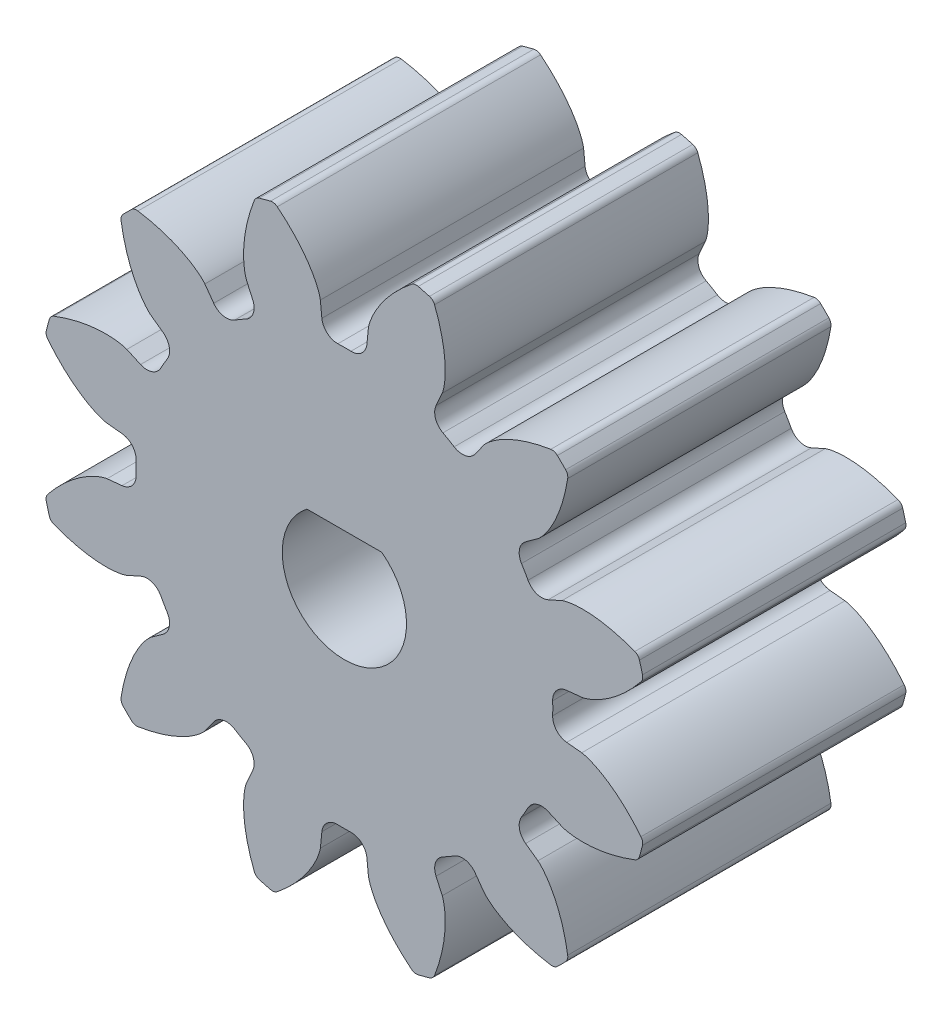
SolidWorks part; units mm, degrees
material "DELRIN"
ref_plane "Front" through (0, 0, 0) normal (0, 0, 1) x (1, 0, 0)
ref_plane "Top" through (0, 0, 0) normal (0, 1, 0) x (1, 0, 0)
ref_plane "Right" through (0, 0, 0) normal (1, 0, 0) x (0, 0, -1)
sketch "Sketch1" plane through (0, 0, 0) normal (0, 0, 1) x (1, 0, 0)
  circle A0 centre (0, 0) radius 14.8167
  dimension "OutsideDiameter" = 29.6333
extrude "Boss-Extrude1" add sketch "Sketch1" along normal blind 12.7
sketch "Sketch3" plane through (0, 0, 0) normal (0, 0, 1) x (1, 0, 0)
  line L0 (0, 0) -> (43.7181, 0) construction
  line L2 (0, 0) -> (-1.013, 10.003) construction
  line L3 (0, 0) -> (1.013, 10.003) construction
  line L4 (1.013, 10.003) -> (1.1597, 11.4515) construction
  line L5 (0, 0) -> (0, 61.276) construction
  line L6 (-1.013, 10.003) -> (-1.1597, 11.4515) construction
  circle A0 centre (0, 0) radius 14.8167 construction
  circle A1 centre (0, 0) radius 12.7 construction
  circle A2 centre (0, 0) radius 11.5101 construction
  arc A3 (1.013, 10.003) -> (-1.013, 10.003) centre (0, 0) ccw construction
  arc A5 (3.383, 14.4253) -> (-3.383, 14.4253) centre (0, 0) ccw
  spline S0 degree 4 poles (-1.1597, 11.4515) (-1.1603, 11.4571) (-1.1625, 11.4726) (-1.1677, 11.5019) (-1.1778, 11.5493) (-1.1932, 11.6092) (-1.2157, 11.6861) (-1.2458, 11.7758) (-1.2825, 11.8733) (-1.3264, 11.9783) (-1.3735, 12.0819) (-1.4237, 12.1841) (-1.4765, 12.2849) (-1.5438, 12.4057) (-1.629, 12.5486) (-1.7352, 12.7127) (-1.8633, 12.8952) (-2.0018, 13.0771) (-2.1447, 13.2526) (-2.2964, 13.4256) (-2.4483, 13.5899) (-2.6134, 13.7559) (-2.7695, 13.9068) (-2.9521, 14.0704) (-3.1018, 14.2009) (-3.3074, 14.367) (-3.4312, 14.4633) (-3.5787, 14.5738) (-3.6457, 14.6217) (-3.6869, 14.6513) knots 0 0 0 0 0 0.005377 0.015084 0.028532 0.04661 0.064855 0.092111 0.119476 0.146842 0.174209 0.201575 0.228941 0.256307 0.307035 0.361767 0.4165 0.471232 0.525964 0.580697 0.635429 0.690161 0.744894 0.799626 0.854358 0.909091 0.954545 1 1 1 1 1 construction
  spline S1 degree 4 poles (-1.1597, 11.4515) (-1.1603, 11.4571) (-1.1625, 11.4726) (-1.1677, 11.5019) (-1.1778, 11.5493) (-1.1932, 11.6092) (-1.2157, 11.6861) (-1.2458, 11.7758) (-1.2825, 11.8733) (-1.3264, 11.9783) (-1.3735, 12.0819) (-1.4237, 12.1841) (-1.4765, 12.2849) (-1.5438, 12.4057) (-1.629, 12.5486) (-1.7352, 12.7127) (-1.8633, 12.8952) (-2.0018, 13.0771) (-2.1447, 13.2526) (-2.2964, 13.4256) (-2.4483, 13.5899) (-2.6134, 13.7559) (-2.7695, 13.9068) (-2.9521, 14.0704) (-3.1018, 14.2009) (-3.2628, 14.331) (-3.3421, 14.3936) (-3.383, 14.4253) knots 0 0 0 0 0 0.005377 0.015084 0.028532 0.04661 0.064855 0.092111 0.119476 0.146842 0.174209 0.201575 0.228941 0.256307 0.307035 0.361767 0.4165 0.471232 0.525964 0.580697 0.635429 0.690161 0.744894 0.799626 0.854358 0.909091 0.909091 0.909091 0.909091 0.909091
  spline S2 degree 4 poles (1.1597, 11.4515) (1.1603, 11.4571) (1.1625, 11.4726) (1.1677, 11.5019) (1.1778, 11.5493) (1.1932, 11.6092) (1.2157, 11.6861) (1.2458, 11.7758) (1.2825, 11.8733) (1.3264, 11.9783) (1.3735, 12.0819) (1.4237, 12.1841) (1.4765, 12.2849) (1.5438, 12.4057) (1.629, 12.5486) (1.7352, 12.7127) (1.8633, 12.8952) (2.0018, 13.0771) (2.1447, 13.2526) (2.2964, 13.4256) (2.4483, 13.5899) (2.6134, 13.7559) (2.7695, 13.9068) (2.9521, 14.0704) (3.1018, 14.2009) (3.3074, 14.367) (3.4312, 14.4633) (3.5787, 14.5738) (3.6457, 14.6217) (3.6869, 14.6513) knots 0 0 0 0 0 0.005377 0.015084 0.028532 0.04661 0.064855 0.092111 0.119476 0.146842 0.174209 0.201575 0.228941 0.256307 0.307035 0.361767 0.4165 0.471232 0.525964 0.580697 0.635429 0.690161 0.744894 0.799626 0.854358 0.909091 0.954545 1 1 1 1 1 construction
  spline S3 degree 4 poles (1.1597, 11.4515) (1.1603, 11.4571) (1.1625, 11.4726) (1.1677, 11.5019) (1.1778, 11.5493) (1.1932, 11.6092) (1.2157, 11.6861) (1.2458, 11.7758) (1.2825, 11.8733) (1.3264, 11.9783) (1.3735, 12.0819) (1.4237, 12.1841) (1.4765, 12.2849) (1.5438, 12.4057) (1.629, 12.5486) (1.7352, 12.7127) (1.8633, 12.8952) (2.0018, 13.0771) (2.1447, 13.2526) (2.2964, 13.4256) (2.4483, 13.5899) (2.6134, 13.7559) (2.7695, 13.9068) (2.9521, 14.0704) (3.1018, 14.2009) (3.2628, 14.331) (3.3421, 14.3936) (3.383, 14.4253) knots 0 0 0 0 0 0.005377 0.015084 0.028532 0.04661 0.064855 0.092111 0.119476 0.146842 0.174209 0.201575 0.228941 0.256307 0.307035 0.361767 0.4165 0.471232 0.525964 0.580697 0.635429 0.690161 0.744894 0.799626 0.854358 0.909091 0.909091 0.909091 0.909091 0.909091
  point P0 (0, 10.0542)
  dimension "OutsideDiameter" = 29.6333
  dimension "PitchCircle" = 25.4
  dimension "BaseCircle" = 23.0202
  dimension "DedendumCircle" = 20.1083
sketch "DCLTBC" plane through (0, 0, 0) normal (0, 0, 1) x (1, 0, 0)
  line L0 (0, 0) -> (41.04, 0) construction
  line L1 (-1.013, 10.003) -> (-1.1597, 11.4515) construction
  line L2 (1.013, 10.003) -> (1.1597, 11.4515) construction
  line L3 (-1.013, 10.003) -> (-1.1597, 11.4515)
  line L4 (1.013, 10.003) -> (1.1597, 11.4515)
  line L5 (0, 0) -> (0, 104.9356) construction
  circle A0 centre (0, 0) radius 14.8167
  circle A1 centre (0, 0) radius 12.7 construction
  circle A2 centre (0, 0) radius 11.5101 construction
  arc A3 (1.013, 10.003) -> (-1.013, 10.003) centre (0, 0) ccw construction
  arc A4 (1.013, 10.003) -> (-1.013, 10.003) centre (0, 0) ccw
  spline S0 degree 4 poles (-994.6421, -102.1305) (-15.3204, 8.3811) (-1.2885, 10.3805) (-1.0584, 10.9911) (-1.1778, 11.5493) (-1.1932, 11.6092) (-1.2157, 11.6861) (-1.2458, 11.7758) (-1.2825, 11.8733) (-1.3264, 11.9783) (-1.3735, 12.0819) (-1.4237, 12.1841) (-1.4765, 12.2849) (-1.5438, 12.4057) (-1.629, 12.5486) (-1.7352, 12.7127) (-1.8633, 12.8952) (-2.0018, 13.0771) (-2.1447, 13.2526) (-2.2964, 13.4256) (-2.4483, 13.5899) (-2.6134, 13.7559) (-2.7695, 13.9068) (-2.9521, 14.0704) (-3.653, 14.6812) (-6.0162, 16.384) (19.2983, -3.4818) (-794.1304, 626.5236) knots -0.502219 -0.502219 -0.502219 -0.502219 -0.502219 0.005377 0.015084 0.028532 0.04661 0.064855 0.092111 0.119476 0.146842 0.174209 0.201575 0.228941 0.256307 0.307035 0.361767 0.4165 0.471232 0.525964 0.580697 0.635429 0.690161 0.744894 0.799626 0.854358 1.715037 1.715037 1.715037 1.715037 1.715037 only from (-1.1597, 11.4515) to (-3.383, 14.4253) construction
  spline S1 degree 4 poles (994.6421, -102.1305) (15.3204, 8.3811) (1.2885, 10.3805) (1.0584, 10.9911) (1.1778, 11.5493) (1.1932, 11.6092) (1.2157, 11.6861) (1.2458, 11.7758) (1.2825, 11.8733) (1.3264, 11.9783) (1.3735, 12.0819) (1.4237, 12.1841) (1.4765, 12.2849) (1.5438, 12.4057) (1.629, 12.5486) (1.7352, 12.7127) (1.8633, 12.8952) (2.0018, 13.0771) (2.1447, 13.2526) (2.2964, 13.4256) (2.4483, 13.5899) (2.6134, 13.7559) (2.7695, 13.9068) (2.9521, 14.0704) (3.653, 14.6812) (6.0162, 16.384) (-19.2983, -3.4818) (794.1304, 626.5236) knots -0.502219 -0.502219 -0.502219 -0.502219 -0.502219 0.005377 0.015084 0.028532 0.04661 0.064855 0.092111 0.119476 0.146842 0.174209 0.201575 0.228941 0.256307 0.307035 0.361767 0.4165 0.471232 0.525964 0.580697 0.635429 0.690161 0.744894 0.799626 0.854358 1.715037 1.715037 1.715037 1.715037 1.715037 only from (1.1597, 11.4515) to (3.383, 14.4253) construction
  spline S2 degree 4 poles (-1.1597, 11.4515) (-1.1603, 11.4571) (-1.1625, 11.4726) (-1.1677, 11.5019) (-1.1778, 11.5493) (-1.1932, 11.6092) (-1.2157, 11.6861) (-1.2458, 11.7758) (-1.2825, 11.8733) (-1.3264, 11.9783) (-1.3735, 12.0819) (-1.4237, 12.1841) (-1.4765, 12.2849) (-1.5438, 12.4057) (-1.629, 12.5486) (-1.7352, 12.7127) (-1.8633, 12.8952) (-2.0018, 13.0771) (-2.1447, 13.2526) (-2.2964, 13.4256) (-2.4483, 13.5899) (-2.6134, 13.7559) (-2.7695, 13.9068) (-2.9521, 14.0704) (-3.1018, 14.2009) (-3.2628, 14.331) (-3.3421, 14.3936) (-3.383, 14.4253) knots 0 0 0 0 0 0.005377 0.015084 0.028532 0.04661 0.064855 0.092111 0.119476 0.146842 0.174209 0.201575 0.228941 0.256307 0.307035 0.361767 0.4165 0.471232 0.525964 0.580697 0.635429 0.690161 0.744894 0.799626 0.854358 0.909091 0.909091 0.909091 0.909091 0.909091
  spline S3 degree 4 poles (1.1597, 11.4515) (1.1603, 11.4571) (1.1625, 11.4726) (1.1677, 11.5019) (1.1778, 11.5493) (1.1932, 11.6092) (1.2157, 11.6861) (1.2458, 11.7758) (1.2825, 11.8733) (1.3264, 11.9783) (1.3735, 12.0819) (1.4237, 12.1841) (1.4765, 12.2849) (1.5438, 12.4057) (1.629, 12.5486) (1.7352, 12.7127) (1.8633, 12.8952) (2.0018, 13.0771) (2.1447, 13.2526) (2.2964, 13.4256) (2.4483, 13.5899) (2.6134, 13.7559) (2.7695, 13.9068) (2.9521, 14.0704) (3.1018, 14.2009) (3.2628, 14.331) (3.3421, 14.3936) (3.383, 14.4253) knots 0 0 0 0 0 0.005377 0.015084 0.028532 0.04661 0.064855 0.092111 0.119476 0.146842 0.174209 0.201575 0.228941 0.256307 0.307035 0.361767 0.4165 0.471232 0.525964 0.580697 0.635429 0.690161 0.744894 0.799626 0.854358 0.909091 0.909091 0.909091 0.909091 0.909091
  dimension "OutsideDiameter" = 29.6333
  dimension "PitchCircle" = 25.4
  dimension "BaseCircle" = 23.0202
extrude "Cut-Extrude-DCLTBC" cut sketch "DCLTBC" along normal through all contours L4 S3 A0 S2 L3 A4 region at (0, 12.9077, 0)
fillet "Fillet-Tip-DCLTBC" radius 0.3764 2 edges at (3.383, 14.4253, 6.35) (-3.383, 14.4253, 6.35)
fillet "Fillet-Root-DCLTBC" radius 0.7528 2 edges at (-1.013, 10.003, 6.35) (1.013, 10.003, 6.35)
pattern_circular "CirPattern-DCLTBC" count 12 over 360 about axis through (0, 0, 12.7) along (0, 0, 1) of "Cut-Extrude-DCLTBC", "Fillet-Tip-DCLTBC", "Fillet-Root-DCLTBC"
sketch "DCGTBC" [suppressed] plane through (0, 0, 0) normal (0, 0, 1) x (1, 0, 0)
  line L0 (0, 0) -> (41.04, 0) construction
  line L1 (-60.6226, 5.3038) -> (0, 0) construction
  line L2 (0, 0) -> (60.6226, 5.3038) construction
  line L3 (0, 0) -> (-16.5124, 0)
  line L5 (0, 0) -> (0, 104.9356) construction
  circle A0 centre (0, 0) radius 65.6167
  circle A1 centre (0, 0) radius 63.5 construction
  circle A2 centre (0, 0) radius 57.5505 construction
  arc A3 (-0.231, 60.8537) -> (0.231, 60.8537) centre (0, 0) ccw construction
  arc A11 (60.6226, 5.3038) -> (-60.6226, 5.3038) centre (0, 0) ccw
  spline S4 degree 4 poles (999.5281, 37.5164) (15.9379, 54.4029) (0.0707, 55.4419) (-0.2895, 56.6024) (-0.2066, 57.7767) (-0.1929, 57.9173) (-0.1708, 58.0988) (-0.1393, 58.3123) (-0.0988, 58.5468) (-0.0484, 58.8015) (0.0074, 59.0552) (0.0683, 59.3079) (0.1336, 59.5593) (0.2182, 59.8633) (0.3273, 60.227) (0.4659, 60.6511) (0.6363, 61.1305) (0.824, 61.6174) (1.0202, 62.0951) (1.2316, 62.5758) (1.4455, 63.0396) (1.6812, 63.5192) (1.9056, 63.9609) (2.1719, 64.4533) (3.0421, 66.0274) (5.6872, 70.2084) (-15.0429, 35.5301) (520.7458, 920.9699) knots -0.449335 -0.449335 -0.449335 -0.449335 -0.449335 0.005377 0.015084 0.028532 0.04661 0.064855 0.092111 0.119476 0.146842 0.174209 0.201575 0.228941 0.256307 0.307035 0.361767 0.4165 0.471232 0.525964 0.580697 0.635429 0.690161 0.744894 0.799626 0.854358 1.559054 1.559054 1.559054 1.559054 1.559054 only from (-0.2184, 57.5501) to (2.8092, 65.5565) construction
  spline S5 degree 4 poles (-999.5281, 37.5164) (-15.9379, 54.4029) (-0.0707, 55.4419) (0.2895, 56.6024) (0.2066, 57.7767) (0.1929, 57.9173) (0.1708, 58.0988) (0.1393, 58.3123) (0.0988, 58.5468) (0.0484, 58.8015) (-0.0074, 59.0552) (-0.0683, 59.3079) (-0.1336, 59.5593) (-0.2182, 59.8633) (-0.3273, 60.227) (-0.4659, 60.6511) (-0.6363, 61.1305) (-0.824, 61.6174) (-1.0202, 62.0951) (-1.2316, 62.5758) (-1.4455, 63.0396) (-1.6812, 63.5192) (-1.9056, 63.9609) (-2.1719, 64.4533) (-3.0421, 66.0274) (-5.6872, 70.2084) (15.0429, 35.5301) (-520.7458, 920.9699) knots -0.449335 -0.449335 -0.449335 -0.449335 -0.449335 0.005377 0.015084 0.028532 0.04661 0.064855 0.092111 0.119476 0.146842 0.174209 0.201575 0.228941 0.256307 0.307035 0.361767 0.4165 0.471232 0.525964 0.580697 0.635429 0.690161 0.744894 0.799626 0.854358 1.559054 1.559054 1.559054 1.559054 1.559054 only from (0.2184, 57.5501) to (-2.8092, 65.5565) construction
  spline S6 degree 4 poles (-0.2184, 57.5501) (-0.2183, 57.5629) (-0.2176, 57.5987) (-0.2144, 57.6663) (-0.2066, 57.7767) (-0.1929, 57.9173) (-0.1708, 58.0988) (-0.1393, 58.3123) (-0.0988, 58.5468) (-0.0484, 58.8015) (0.0074, 59.0552) (0.0683, 59.3079) (0.1336, 59.5593) (0.2182, 59.8633) (0.3273, 60.227) (0.4659, 60.6511) (0.6363, 61.1305) (0.824, 61.6174) (1.0202, 62.0951) (1.2316, 62.5758) (1.4455, 63.0396) (1.6812, 63.5192) (1.9056, 63.9609) (2.1719, 64.4533) (2.3911, 64.8499) (2.63, 65.2574) (2.7481, 65.4554) (2.8092, 65.5565) knots 0 0 0 0 0 0.005377 0.015084 0.028532 0.04661 0.064855 0.092111 0.119476 0.146842 0.174209 0.201575 0.228941 0.256307 0.307035 0.361767 0.4165 0.471232 0.525964 0.580697 0.635429 0.690161 0.744894 0.799626 0.854358 0.909091 0.909091 0.909091 0.909091 0.909091
  spline S7 degree 4 poles (0.2184, 57.5501) (0.2183, 57.5629) (0.2176, 57.5987) (0.2144, 57.6663) (0.2066, 57.7767) (0.1929, 57.9173) (0.1708, 58.0988) (0.1393, 58.3123) (0.0988, 58.5468) (0.0484, 58.8015) (-0.0074, 59.0552) (-0.0683, 59.3079) (-0.1336, 59.5593) (-0.2182, 59.8633) (-0.3273, 60.227) (-0.4659, 60.6511) (-0.6363, 61.1305) (-0.824, 61.6174) (-1.0202, 62.0951) (-1.2316, 62.5758) (-1.4455, 63.0396) (-1.6812, 63.5192) (-1.9056, 63.9609) (-2.1719, 64.4533) (-2.3911, 64.8499) (-2.63, 65.2574) (-2.7481, 65.4554) (-2.8092, 65.5565) knots 0 0 0 0 0 0.005377 0.015084 0.028532 0.04661 0.064855 0.092111 0.119476 0.146842 0.174209 0.201575 0.228941 0.256307 0.307035 0.361767 0.4165 0.471232 0.525964 0.580697 0.635429 0.690161 0.744894 0.799626 0.854358 0.909091 0.909091 0.909091 0.909091 0.909091
  dimension "D1" = 5
  dimension "D2" = 5
  dimension "OutsideDiameter" = 29.6333
  dimension "PitchCircle" = 25.4
  dimension "BaseCircle" = 23.0202
extrude "Cut-Extrude-DCGTBC" [suppressed] cut sketch "DCGTBC" along normal through all
fillet "Fillet-Tip-DCGTBC" [suppressed] radius 0.3764
pattern_circular "CirPattern-DCGTBC" [suppressed] count 12 over 360 of bodies 112
sketch "Sketch8" plane through (0, 0, 0) normal (0, 0, 1) x (1, 0, 0)
  line L0 (18.125, -4.6) -> (21.725, -4.6)
  line L1 (-1.8034, 2.3939) -> (1.8034, 2.3939)
  circle A2 centre (19.925, -7) radius 3
  circle A3 centre (0, 0) radius 2.9972
  dimension "D1" = 6
  dimension "D2" = 5.9944
  dimension "D3" = 3.6
  dimension "D4" = 3.6068
extrude "Cut-Extrude5" cut sketch "Sketch8" along normal blind 25.4 contours A3 region at (0, -0.1462, 0)
equation "\"DiametralPitch\"= 12'Diametral Pitch"
equation "\"NumTeeth\"= 12'Number of Teeth"
equation "\"PressureAngle\"= 25deg'Pressure Angle"
equation "\"Addendum\"= 1 / \"DiametralPitch\"'Addendum"
equation "\"Dedendum\"= 1.25 / \"DiametralPitch\"'Dedendum"
equation "\"WorkingDepth\"= 2 / \"DiametralPitch\"'Working Depth - here for REF (Not used in building model)"
equation "\"WholeDepth\"= 2.25 / \"DiametralPitch\"'Whole Depth - here for REF (Not used in building model)"
equation "\"Clearance\"= .25 / \"DiametralPitch\"'Clearance"
equation "\"CircularPitch\"= pi / \"DiametralPitch\"'Circular Pitch - here for REF (Not used in building model)"
equation "\"PitchCircle\"= \"NumTeeth\" / \"DiametralPitch\"'Pitch Circle - or - Pitch Diameter"
equation "\"OutsideDiameter\"= ( \"NumTeeth\" + 2 ) / \"DiametralPitch\"'Outside Diameter"
equation "\"Fillet_Root\"= \"Clearance\" * cos ( \"PressureAngle\" ) * tan ( ( 90 + \"PressureAngle\" ) / 2 ) 'Fillet Root"
equation "\"AddendumCircle\"= \"PitchCircle\" + ( 2 * \"Addendum\" )'Addendum Circle - or - Addendum Diameter"
equation "\"DedendumCircle\"= \"PitchCircle\" - ( 2 * \"Dedendum\" )'Dedendum Circle - or - Dedendum Diameter"
equation "\"BaseCircle\"= \"PitchCircle\" * cos ( \"PressureAngle\" )'Base Circle - Base Diameter"
equation "\"PitchAngle\"= 360deg / \"NumTeeth\"'Pitch Angle"
equation "\"Alpha\"= sqr ( \"PitchCircle\" ^ 2 - \"BaseCircle\" ^ 2 ) / \"BaseCircle\" * 180 / PI - \"PressureAngle\"'Alpha - Used for Calculating Beta"
equation "\"Beta\"= ( \"PitchAngle\" / 4 - ( \"Alpha\" - 90 ) )'Beta - Used in definition of the parameters for the parametric equation driven curve"
equation "\"Gamma\"= ( \"PitchAngle\" / 4 - ( \"Alpha\" + 90 ) )'Gamma - Used in definition of the parameters for the parametric equation driven curve"
equation "\"Phi\"= sqr ( ( \"AddendumCircle\" / 2 ) ^ 2 - ( \"BaseCircle\" / 2 ) ^ 2 ) / ( \"BaseCircle\" / 2 )'Phi - Used in definition of the parameters for the parametric equation driven curve"
equation "\"DCGTBC\"= iif ( \"DedendumCircle\" > \"BaseCircle\" , \"unsuppressed\" , \"suppressed\" )'if Dedendum Circle IS GREATER THAN BaseCircle THEN UnsuppressORSuppress FEATURE"
equation "\"DCLTBC\"= iif ( \"DedendumCircle\" - .002 > \"BaseCircle\" , \"suppressed\" , \"unsuppressed\" )'if Dedendum Circle - .002 IS GREATER THAN BaseCircle THEN SuppressORUnsuppress FEATURE"
equation "\"Cut-Extrude-DCGTBC\"= iif ( \"DedendumCircle\" > \"BaseCircle\" , \"unsuppressed\" , \"suppressed\" )'if Dedendum Circle IS GREATER THAN BaseCircle THEN UnsuppressORSuppress FEATURE"
equation "\"Cut-Extrude-DCLTBC\"= iif ( \"DedendumCircle\" - .002 > \"BaseCircle\" , \"suppressed\" , \"unsuppressed\" )'if Dedendum Circle - .002 IS GREATER THAN BaseCircle THEN SuppressORUnsuppress FEATURE"
equation "\"CirPattern-DCGTBC\"= iif ( \"DedendumCircle\" > \"BaseCircle\" , \"unsuppressed\" , \"suppressed\" )'if Dedendum Circle IS GREATER THAN BaseCircle THEN UnsuppressORSuppress FEATURE"
equation "\"CirPattern-DCLTBC\"= iif ( \"DedendumCircle\" - .002 > \"BaseCircle\" , \"suppressed\" , \"unsuppressed\" )'if Dedendum Circle - .002 IS GREATER THAN BaseCircle THEN SuppressORUnsuppress FEATURE"
equation "\"Fillet-Tip-DCGTBC\"= iif ( \"DedendumCircle\" > \"BaseCircle\" , \"unsuppressed\" , \"suppressed\" )'if Dedendum Circle IS GREATER THAN BaseCircle THEN UnsuppressORSuppress FEATURE"
equation "\"Fillet-Tip-DCLTBC\"= iif ( \"DedendumCircle\" - .002 > \"BaseCircle\" , \"suppressed\" , \"unsuppressed\" )'if Dedendum Circle - .002 IS GREATER THAN BaseCircle THEN SuppressORUnsuppress FEATURE"
equation "\"Fillet-Root-DCLTBC\"= iif ( \"DedendumCircle\" - .002 > \"BaseCircle\" , \"suppressed\" , \"unsuppressed\" )'if Dedendum Circle - .002 IS GREATER THAN BaseCircle THEN SuppressORUnsuppress FEATURE"
equation "\"D1@CirPattern-DCGTBC\"= \"NumTeeth\"'Number of Teeth"
equation "\"D1@CirPattern-DCLTBC\"= \"NumTeeth\"'Number of Teeth"
equation "\"D1@Fillet-Tip-DCGTBC\"= \"Fillet_Root\" / 2 'Tip Rad For Large No of Teeth"
equation "\"D1@Fillet-Tip-DCLTBC\"=\"Fillet_Root\" / 2'Tip Rad For Small No of Teeth"
equation "\"D1@Fillet-Root-DCLTBC\"= \"Fillet_Root\"'Fillet Root"
